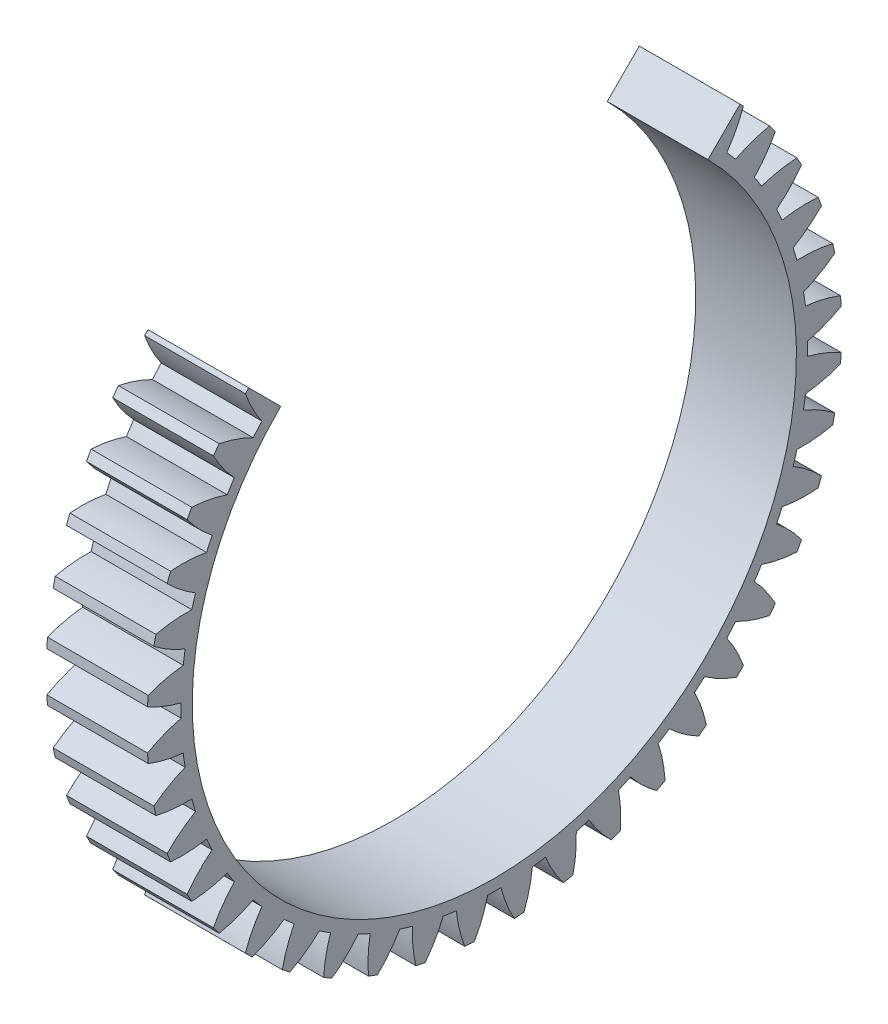
SolidWorks part; units mm, degrees
ref_plane "Plane1" through (0, 0, 0) normal (0, 0, 1) x (1, 0, 0)
ref_plane "Plane2" through (0, 0, 0) normal (0, 1, 0) x (1, 0, 0)
ref_plane "Plane3" through (0, 0, 0) normal (1, 0, 0) x (0, 0, -1)
other "Configuration Table"
sketch "HoldingSke" plane through (0, 0, 0) normal (0, 1, 0) x (1, 0, 0)
  line L0 (0, 0) -> (0.4796, -0.4631)
  line L1 (-15, 0) -> (100, 0) construction
  line L2 (0, 0) -> (-2.1039, 2.3779)
  line L3 (0, 0) -> (-11.863, 4.5341)
  line L4 (0, 0) -> (6.2122, 5.9991)
  line L5 (0, 0) -> (-46.8476, -17.4728)
  line L6 (0, 0) -> (-8.2896, -5.593)
  line L7 (-2.1039, 2.3779) -> (8.6586, 51.2059)
  line L8 (-76.2, 54.61) -> (-71.8, 54.61)
  line L9 (-71.009, 38.7566) -> (-53.1078, 45.2721)
  line L10 (-76.2, 71.12) -> (104.1128, 71.12)
  line L11 (0, 0) -> (-10, 0)
  line L12 (-76.2, 101.6) -> (-76.147, 101.6)
  line L13 (24.9733, 27.94) -> (52.9518, 28.4284)
  line L14 (24.9733, 27.94) -> (24.9743, 27.94)
  line L15 (24.9733, 27.94) -> (100.4006, 29.5858)
  line L16 (-63.627, -1.5) -> (-12.827, -1.5)
  circle A0 centre (0, 0) radius 30
  circle A1 centre (0, 0) radius 31.124
  circle A2 centre (0, 0) radius 37.5
  circle A3 centre (0, 0) radius 30
  dimension "Num_teeth" = 44
  dimension "Pitch_radius" = 180.3128
  dimension "Width" = 10
  dimension "Thickness" = 10
sketch "BasProSke" plane through (0, 0, 0) normal (0, 1, 0) x (1, 0, 0)
  line L0 (-10, 0) -> (60, 0) construction
  line L1 (0, 0) -> (0, 34.5)
  line L2 (0, 0) -> (10, 0)
  line L3 (10, 0) -> (10, 34.5)
  line L4 (10, 34.5) -> (0, 34.5)
  dimension "Thickness" = 10
  dimension "Diameter" = 69
revolve "Base-Revolve" add sketch "BasProSke" angle 360 about L0
sketch "TooCutSke" plane through (0, 0, 0) normal (1, 0, 0) x (0, 0, -1)
  line L1 (0, 0) -> (0, 107) construction
  line L2 (0, 0) -> (-1.2706, 32.9755) construction
  line L3 (0, 0) -> (-4.7058, 65.7962) construction
  line L4 (-1.2706, 32.9755) -> (-2.3529, 32.8981) construction
  arc A0 (0.6591, 31.117) -> (-0.6591, 31.117) centre (0, 0) ccw
  arc A1 (2.0005, 34.4674) -> (-2.0005, 34.4674) centre (0, 0) ccw
  circle A2 centre (0, 0) radius 33 construction
  circle A3 centre (0, 0) radius 31.0099 construction
  arc A4 (-0.6591, 31.117) -> (-2.0005, 34.4674) centre (-13.4691, 27.932) ccw
  arc A5 (2.0005, 34.4674) -> (0.6591, 31.117) centre (13.4691, 27.932) ccw
extrude "ToothCut" cut sketch "TooCutSke" along normal through all
fillet "Breaks" [suppressed] radius 0.03 tangent propagation no
fillet "RootFillets" [suppressed] radius 0.376
pattern_circular "TeethCuts" count 44 every 8.182 about axis through (-10, 0, 0) along (1, 0, 0) of "ToothCut", "RootFillets", "Breaks"
sketch "HubNeaOneSke" plane through (0, 0, 0) normal (-1, 0, 0) x (0, 0, 1)
  circle A0 centre (0, 0) radius 31.124
  dimension "Diameter" = 62.248
extrude "HubNearOne" [suppressed] add sketch "HubNeaOneSke" along normal blind 40.0001
sketch "HubNeaBotSke" plane through (0, 0, 0) normal (-1, 0, 0) x (0, 0, 1)
  circle A0 centre (0, 0) radius 31.124
  dimension "Diameter" = 62.248
extrude "HubNearBoth" [suppressed] add sketch "HubNeaBotSke" along normal blind 20
ref_plane "FarPln" through (10, 0, 0) normal (1, 0, 0) x (0, 0, -1)
sketch "HubFarSke" plane through (10, 0, 0) normal (1, 0, 0) x (0, 0, -1)
  circle A0 centre (0, 0) radius 31.124
  dimension "Diameter" = 62.248
extrude "HubFar" [suppressed] add sketch "HubFarSke" along normal blind 20
sketch "BorSke" plane through (0, 0, 0) normal (1, 0, 0) x (0, 0, -1)
  circle A0 centre (0, 0) radius 30
  dimension "Diameter" = 60
extrude "Bore" cut sketch "BorSke" along normal mid plane 100.0001
sketch "KeySke" plane through (0, 0, 0) normal (1, 0, 0) x (0, 0, -1)
  line L0 (-9, 0) -> (-9, 34.4)
  line L1 (-9, 34.4) -> (9, 34.4)
  line L2 (9, 34.4) -> (9, 0)
  line L3 (0, 0) -> (0, 34) construction
  line L4 (-9, 0) -> (9, 0)
  dimension "Width" = 18
extrude "Keyway" [suppressed] cut sketch "KeySke" along normal mid plane 100.0001
pattern_circular "Keyway2" [suppressed] count 2 every 90 about axis through (-10, 0, 0) along (1, 0, 0)
sketch "Sketch1" plane through (10, 0, 0) normal (1, 0, 0) x (0, 0, -1)
  line L0 (-24.3952, 24.3952) -> (-21.2132, 21.2132)
  line L1 (-21.2132, 21.2132) -> (0, 0) construction
  line L2 (0, 0) -> (21.2132, 21.2132) construction
  line L3 (24.3952, 24.3952) -> (21.2132, 21.2132)
  line L4 (0, 0) -> (0, 34.5) construction
  arc A0 (-24.3952, 24.3952) -> (24.3952, 24.3952) centre (0, 0) cw
  arc A1 (-21.2132, 21.2132) -> (21.2132, 21.2132) centre (0, 0) cw
  circle A2 centre (0, 0) radius 30 construction
  arc A3 (-1.9865, 34.4428) -> (-2.9355, 34.3749) centre (0, 0) ccw construction
  point P11 (-2.4612, 34.4121)
  dimension "D1" = 45
  dimension "D2" = 45
extrude "Cut-Extrude1" cut sketch "Sketch1" against normal through all
equation "' \"Module@HoldingSke\" = 6.35"
equation "' \"Num_teeth@HoldingSke\" = 12"
equation "' \"Ap@HoldingSke\" =  20"
equation "' \"Ap@HoldingSke\" = 20"
equation "' \"Width@HoldingSke\" = 0.5 * 25.4"
equation "' \"Hub_dia@HoldingSke\"= 1 * 25.4"
equation "' \"Hub_dia@HoldingSke\" = 1 * 25.4"
equation "' \"Overall_len@HoldingSke\" = 1.0 * 25.4"
equation "' \"Bore@HoldingSke\" = 0.75 * 25.4"
equation "' \"T_dim@HoldingSke\" = 0.1 * 25.4"
equation "' \"Width@KeySke\" = 0.25 * 25.4"
equation "' \"Show_teeth@HoldingSke\" = 13"
equation "' \"Backlash@HoldingSke\" = 0.009 * 25.4"
equation "' \"Addendum_fac@HoldingSke\" = 1.0"
equation "' \"Dedendum_fac@HoldingSke\" = 1.25"
equation "' \"Dedendum_add@HoldingSke\" = 0.00005 * 25.4"
equation "' \"Clearance_fac@HoldingSke\" = 0.25"
equation "\"Pitch@HoldingSke\" = 1 / \"Module@HoldingSke\""
equation "\"Overcut_dia@TooCutSke\" = (\"Num_teeth@HoldingSke\" + 2 * \"Addendum_fac@HoldingSke\") / \"Pitch@HoldingSke\" + 0.002 * 25.4"
equation "\"Pitch_dia@TooCutSke\" = \"Num_teeth@HoldingSke\" / \"Pitch@HoldingSke\""
equation "\"Base_dia@TooCutSke\" = \"Num_teeth@HoldingSke\" / \"Pitch@HoldingSke\" * cos((\"Ap@HoldingSke\"  * 3.14159265 / 180))"
equation "\"Root_dia@TooCutSke\" = (\"Num_teeth@HoldingSke\" + 2) / \"Pitch@HoldingSke\" - 2 * (\"Addendum_fac@HoldingSke\" + \"Dedendum_fac@HoldingSke\") / \"Pitch@HoldingSke\" - \"Dedendum_add@HoldingSke\" * 2"
equation "\"Half_ang@TooCutSke\" = 180 / \"Num_teeth@HoldingSke\""
equation "\"Half_CT@TooCutSke\" = \"Num_teeth@HoldingSke\" / \"Pitch@HoldingSke\" * sin((3.14159265 / 2 / \"Num_teeth@HoldingSke\")) / 2 - 7 * \"Backlash@HoldingSke\" / 4"
equation "\"Flank_rad@TooCutSke\" = \"Num_teeth@HoldingSke\" / \"Pitch@HoldingSke\" / 5"
equation "\"Radius@RootFillets\" = \"Clearance_fac@HoldingSke\" / \"Pitch@HoldingSke\" + \"Dedendum_add@HoldingSke\""
equation "\"Break_rad@Breaks\" = 0.02 / \"Pitch@HoldingSke\""
equation "\"Thickness@HoldingSke\" = \"Width@HoldingSke\""
equation "\"OAL@HoldingSke\" = \"Thickness@HoldingSke\""
equation "\"MHD@HoldingSke\" = (\"Num_teeth@HoldingSke\" + 2) / \"Pitch@HoldingSke\" - 2 * (\"Addendum_fac@HoldingSke\" + \"Dedendum_fac@HoldingSke\")  / \"Pitch@HoldingSke\" - \"Dedendum_add@HoldingSke\" * 2"
equation "\"MBD@HoldingSke\" = (\"Num_teeth@HoldingSke\" + 2) / \"Pitch@HoldingSke\" - 2 * (\"Addendum_fac@HoldingSke\" + \"Dedendum_fac@HoldingSke\")  / \"Pitch@HoldingSke\" - \"Dedendum_add@HoldingSke\" * 2 - 0.002 * 25.4"
equation "\"MHD@HoldingSke\" = ((sgn( \"MHD@HoldingSke\" - \"Hub_dia@HoldingSke\" )-1)*( \"MHD@HoldingSke\" - \"Hub_dia@HoldingSke\" ))/-2+ \"Hub_dia@HoldingSke\""
equation "\"MBD@HoldingSke\" = ((sgn( \"MBD@HoldingSke\" - \"Bore@HoldingSke\" )-1)*( \"MBD@HoldingSke\" - \"Bore@HoldingSke\" ))/-2+ \"Bore@HoldingSke\""
equation "\"OAL@HoldingSke\" = ((sgn( \"OAL@HoldingSke\" - \"Overall_len@HoldingSke\" )+1)*( \"OAL@HoldingSke\" - \"Overall_len@HoldingSke\" ))/2 + \"Overall_len@HoldingSke\" + 0.000002 * 25.4"
equation "\"Num_teeth@TeethCuts\" = int( \"Show_teeth@HoldingSke\" ) + 1"
equation "\"Num_teeth@TeethCuts\" = ((sgn( \"Num_teeth@TeethCuts\" - \"Num_teeth@HoldingSke\" )-1)*( \"Num_teeth@TeethCuts\" - \"Num_teeth@HoldingSke\" ))/-2+ \"Num_teeth@HoldingSke\""
equation "\"Num_teeth@TeethCuts\" = ((sgn( \"Num_teeth@TeethCuts\" - 2.0)+1)*( \"Num_teeth@TeethCuts\" - 2.0))/2 +2.0"
equation "\"Angle@TeethCuts\" = 360.0 / \"Num_teeth@HoldingSke\""
equation "\"Diameter@BasProSke\" = (\"Num_teeth@HoldingSke\" + 2 * \"Addendum_fac@HoldingSke\") / \"Pitch@HoldingSke\""
equation "\"Thickness@BasProSke\"  = \"Thickness@HoldingSke\""
equation "' \"Fillet_rad@BasProSke\" =  \"Thickness@HoldingSke\" * 0.05"
equation "' \"Fillet_rad@BasProSke\" = \"Thickness@HoldingSke\" * 0.05"
equation "\"MHD@HoldingSke\" = ((sgn( \"MHD@HoldingSke\" - \"Root_dia@TooCutSke\" )-1)*( \"MHD@HoldingSke\" - \"Root_dia@TooCutSke\" ))/-2+ \"Root_dia@TooCutSke\""
equation "\"Diameter@HubNeaOneSke\" = \"MHD@HoldingSke\""
equation "\"Length@HubNearOne\" = \"OAL@HoldingSke\" - \"Thickness@BasProSke\""
equation "\"Diameter@HubNeaBotSke\" = \"MHD@HoldingSke\""
equation "\"Length@HubNearBoth\" = ( \"OAL@HoldingSke\" - \"Thickness@BasProSke\" ) / 2.0"
equation "\"Thickness@FarPln\" = \"Thickness@BasProSke\""
equation "\"Diameter@HubFarSke\" = \"MHD@HoldingSke\""
equation "\"Length@HubFar\" = ( \"OAL@HoldingSke\" - \"Thickness@BasProSke\" ) / 2.0"
equation "\"Diameter@BorSke\" = \"MBD@HoldingSke\""
equation "\"D1@Bore\" = \"OAL@HoldingSke\" * 2.0"
equation "\"D1@Keyway\" = \"OAL@HoldingSke\" * 2.0"
equation "\"Offset@KeySke\" = \"T_dim@HoldingSke\" + \"MBD@HoldingSke\" / 2.0"
